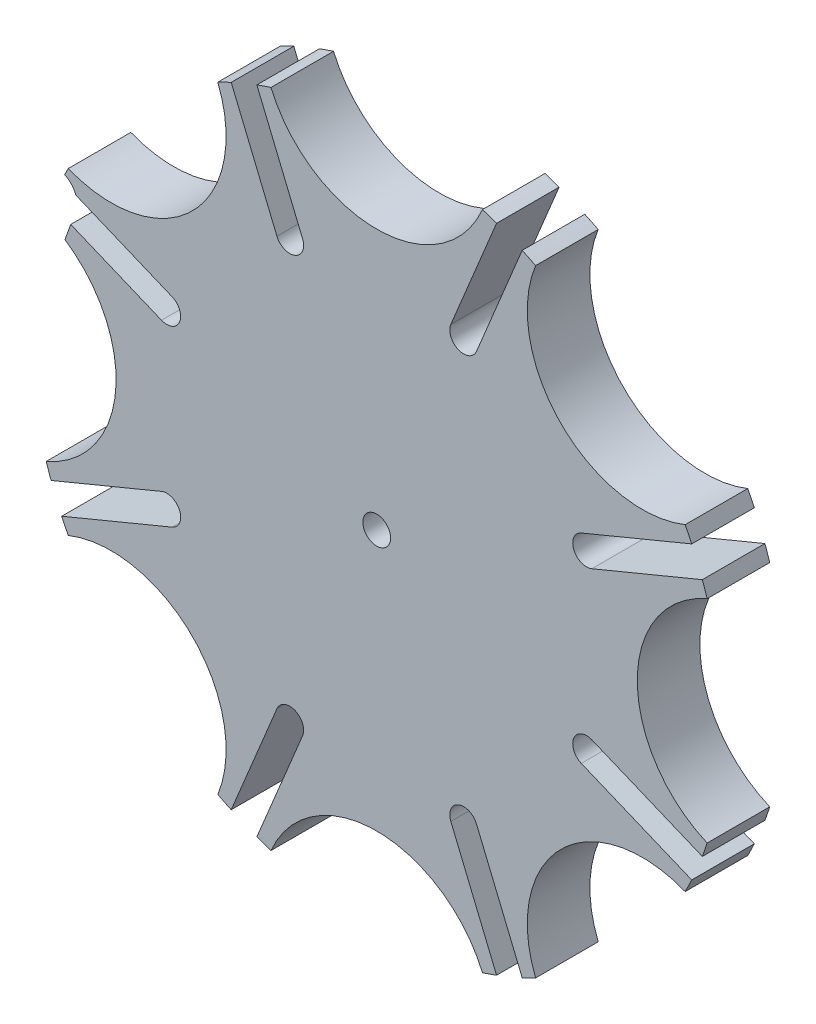
SolidWorks part; units mm, degrees
ref_plane "Front Plane" through (0, 0, 0) normal (0, 0, 1) x (1, 0, 0)
ref_plane "Top Plane" through (0, 0, 0) normal (0, 1, 0) x (1, 0, 0)
ref_plane "Right Plane" through (0, 0, 0) normal (1, 0, 0) x (0, 0, -1)
sketch "Croquis1" plane through (0, 0, 0) normal (0, 0, 1) x (1, 0, 0)
  line L0 (0, 0) -> (-15.1187, 6.2624) construction
  line L1 (0, 0) -> (-18, 0) construction
  line L2 (0, 0) -> (33.8007, 14.0007) construction
  line L3 (0, 0) -> (-10.0606, 4.1672)
  line L4 (-10.0606, 4.1672) -> (-15.364, 6.364) construction
  line L5 (-10.3151, 3.5527) -> (-15.6185, 5.7494)
  line L6 (-9.806, 4.7818) -> (-15.1094, 6.9785)
  line L7 (-18, 0) -> (-15.364, 6.364) construction
  line L8 (-4.1672, 10.0606) -> (-6.364, 15.364) construction
  line L9 (-4.7818, 9.806) -> (-6.9785, 15.1094)
  line L10 (-3.5527, 10.3151) -> (-5.7494, 15.6185)
  line L11 (4.1672, 10.0606) -> (6.364, 15.364) construction
  line L12 (3.5527, 10.3151) -> (5.7494, 15.6185)
  line L13 (4.7818, 9.806) -> (6.9785, 15.1094)
  line L14 (10.0606, 4.1672) -> (15.364, 6.364) construction
  line L45 (-16.2663, 6.7899) -> (-19.2031, 0.5679)
  line L46 (-16.7477, -0.4492) -> (-14.4248, 6.0271)
  line L60 (9.806, 4.7818) -> (15.1094, 6.9785)
  line L75 (10.3151, 3.5527) -> (15.6185, 5.7494)
  line L82 (10.0606, -4.1672) -> (15.364, -6.364) construction
  line L85 (10.3151, -3.5527) -> (15.6185, -5.7494)
  line L88 (9.806, -4.7818) -> (15.1094, -6.9785)
  line L91 (4.1672, -10.0606) -> (6.364, -15.364) construction
  line L92 (4.7818, -9.806) -> (6.9785, -15.1094)
  line L93 (3.5527, -10.3151) -> (5.7494, -15.6185)
  line L94 (-4.1672, -10.0606) -> (-6.364, -15.364) construction
  line L95 (-3.5527, -10.3151) -> (-5.7494, -15.6185)
  line L96 (-4.7818, -9.806) -> (-6.9785, -15.1094)
  line L97 (-10.0606, -4.1672) -> (-15.364, -6.364) construction
  line L98 (-9.806, -4.7818) -> (-15.1094, -6.9785)
  line L99 (-10.3151, -3.5527) -> (-15.6185, -5.7494)
  circle A0 centre (0, 0) radius 16.6298
  circle A7 centre (-18, 0) radius 5.5106
  arc A8 (-10.3151, 3.5527) -> (-9.806, 4.7818) centre (-10.0606, 4.1672) ccw
  arc A9 (-15.1094, 6.9785) -> (-15.6185, 5.7494) centre (-15.364, 6.364) ccw
  circle A10 centre (-12.7279, 12.7279) radius 5.5106
  arc A11 (-4.7818, 9.806) -> (-3.5527, 10.3151) centre (-4.1672, 10.0606) ccw
  arc A12 (-5.7494, 15.6185) -> (-6.9785, 15.1094) centre (-6.364, 15.364) ccw
  circle A13 centre (0, 18) radius 5.5106
  arc A14 (3.5527, 10.3151) -> (4.7818, 9.806) centre (4.1672, 10.0606) ccw
  arc A15 (6.9785, 15.1094) -> (5.7494, 15.6185) centre (6.364, 15.364) ccw
  circle A52 centre (-18, 0) radius 1.3304
  circle A53 centre (-15.364, 6.364) radius 0.9978
  circle A54 centre (0, 0) radius 0.6652
  arc A55 (-12.4894, 0) -> (-22.5301, 3.1377) centre (-12.4894, 17.6341) cw
  circle A56 centre (-18, 0) radius 0.6652
  circle A57 centre (-15.364, 6.364) radius 0.6652
  circle A115 centre (12.7279, 12.7279) radius 5.5106
  arc A116 (9.806, 4.7818) -> (10.3151, 3.5527) centre (10.0606, 4.1672) ccw
  arc A117 (15.6185, 5.7494) -> (15.1094, 6.9785) centre (15.364, 6.364) ccw
  circle A118 centre (18, 0) radius 5.5106
  arc A119 (10.3151, -3.5527) -> (9.806, -4.7818) centre (10.0606, -4.1672) ccw
  arc A120 (15.1094, -6.9785) -> (15.6185, -5.7494) centre (15.364, -6.364) ccw
  circle A121 centre (12.7279, -12.7279) radius 5.5106
  arc A122 (4.7818, -9.806) -> (3.5527, -10.3151) centre (4.1672, -10.0606) ccw
  arc A123 (5.7494, -15.6185) -> (6.9785, -15.1094) centre (6.364, -15.364) ccw
  circle A124 centre (0, -18) radius 5.5106
  arc A125 (-3.5527, -10.3151) -> (-4.7818, -9.806) centre (-4.1672, -10.0606) ccw
  arc A126 (-6.9785, -15.1094) -> (-5.7494, -15.6185) centre (-6.364, -15.364) ccw
  circle A127 centre (-12.7279, -12.7279) radius 5.5106
  arc A128 (-9.806, -4.7818) -> (-10.3151, -3.5527) centre (-10.0606, -4.1672) ccw
  arc A129 (-15.6185, -5.7494) -> (-15.1094, -6.9785) centre (-15.364, -6.364) ccw
  point P4 (-12.7123, 5.2656)
  point P14 (12.7123, 5.2656)
  point P15 (0, 0)
  point P18 (-15.364, 6.364)
  point P20 (-5.2656, 12.7123)
  point P29 (5.2656, 12.7123)
  point P44 (12.7123, -5.2656)
  point P47 (0, 0)
  point P55 (5.2656, -12.7123)
  point P64 (-5.2656, -12.7123)
  point P73 (-12.7123, -5.2656)
  dimension "D4" = 11.0213
  dimension "D8" = 0.6652
  dimension "D3" = 2.6608
  dimension "D9" = 1.3304
  dimension "D11" = 1.9956
  dimension "D12" = 17.6341
  dimension "D13" = 1.3304
  dimension "D1" = 18
  dimension "D2" = 22.5
  dimension "D5" = 45
  dimension "D6" = 36.5856
  dimension "D7" = 10.8895
  dimension "D10" = 8
extrude "Saliente-Extruir1" add sketch "Croquis1" against normal blind 3 contours A0 L13 A14 L12 A13 L10 A11 L9 A10 L6 A8 L5 A7 region at (-9.0321, 4.5932, 0)
sketch "Croquis4" [suppressed] plane through (0, 0, 0) normal (0, 0, 1) x (1, 0, 0)
  circle A0 centre (-18, 0) radius 4.9251 construction
  arc A1 (-22.0487, 2.8043) -> (-13.0749, 0) centre (-13.0749, 15.7603) ccw construction
  arc A2 (-22.0487, 2.8043) -> (-13.0749, 0) centre (-18, 0) ccw
  arc A3 (-22.0487, 2.8043) -> (-13.0749, 0) centre (-13.0749, 15.7603) ccw
  circle A4 centre (-18, 0) radius 0.6766 construction
  circle A5 centre (-18, 0) radius 0.6766
  circle A7 centre (-15.8944, 5.7851) radius 0.6766 construction
  circle A9 centre (-15.8944, 5.7851) radius 0.6766
extrude "Saliente-Extruir4" [suppressed] add sketch "Croquis4" against normal blind 3
sketch "Croquis6" [suppressed] plane through (0, 0, 0) normal (0, 0, 1) x (1, 0, 0)
  line L0 (-16.7049, -0.3922) -> (-14.9231, 5.4909) construction
  line L1 (-16.8275, 6.1841) -> (-19.2442, 0.532) construction
  line L2 (-16.7049, -0.3922) -> (-14.9231, 5.4909)
  line L3 (-16.8275, 6.1841) -> (-19.2442, 0.532)
  circle A0 centre (-15.8944, 5.7851) radius 1.0149 construction
  circle A1 centre (-18, 0) radius 1.3532 construction
  arc A2 (-14.9231, 5.4909) -> (-16.8275, 6.1841) centre (-15.8944, 5.7851) ccw
  arc A3 (-19.2442, 0.532) -> (-16.7049, -0.3922) centre (-18, 0) ccw
  circle A6 centre (-18, 0) radius 0.6766 construction
  circle A7 centre (-18, 0) radius 0.6766
extrude "Saliente-Extruir5" [suppressed] add sketch "Croquis6" along normal blind 3
sketch "Croquis7" [suppressed] plane through (0, 0, 0) normal (0, 0, 1) x (1, 0, 0)
  circle A0 centre (0, 0) radius 0.6766 construction
  circle A1 centre (-18, 0) radius 0.6766 construction
  circle A2 centre (0, 0) radius 0.6766
  circle A3 centre (-18, 0) radius 0.6766
extrude "Saliente-Extruir6" [suppressed] add sketch "Croquis7" against normal blind 18 and the other way blind 3
sketch "Croquis8" [suppressed] plane through (0, 0, -18) normal (0, 0, -1) x (-1, 0, 0)
  line L0 (0, -4.9251) -> (18, -4.9251)
  line L1 (0, 4.9251) -> (18, 4.9251)
  circle A0 centre (18, 0) radius 4.9251 construction
  arc A1 (18, -4.9251) -> (18, 4.9251) centre (18, 0) ccw
  arc A2 (0, 4.9251) -> (0, -4.9251) centre (0, 0) ccw
extrude "Saliente-Extruir7" [suppressed] add sketch "Croquis8" along normal blind 6
equation "\"S\"= ( \"d\" - \"a\" ) * 0.98"
equation "\"R\"= \"d\" * cos ( \"Bo\" / 2 ) * 2"
equation "\"n\"= 8"
equation "\"Bo\"= 360 / \"n\""
equation "\"din\"= \"d\" / 10"
equation "\"d\"=18"
equation "\"D4@Croquis1\"= \"D2\""
equation "\"D1@Croquis1\"=\"d\""
equation "\"D2@Croquis1\"=\"Bo\"/2"
equation "\"D5@Croquis1\"=\"Bo\""
equation "\"D6@Croquis1\"=\"R\"*1.1"
equation "\"D7@Croquis1\"=\"S\""
equation "\"R1\"= \"R\" / 50"
equation "\"D8@Croquis1\"=\"R1\""
equation "\"a\"= \"d\" * sin ( \"Bo\" / 2 )"
equation "\"ancho\"= 3"
equation "\"D1@Saliente-Extruir1\"=\"ancho\""
equation "\"D10@Croquis1\"=\"n\""
equation "\"D2\"= 1.6 * \"a\""
equation "\"D3@Croquis1\"=4*\"R1\""
equation "\"D9@Croquis1\"=2*\"R1\""
equation "\"D11@Croquis1\"=3*\"R1\""
equation "\"D12@Croquis1\"=\"D2\"/2*3.2"
equation "\"D13@Croquis1\"=2*\"R1\""
equation "\"D1@Saliente-Extruir7\"=\"ancho\"*2"
equation "\"D1@Saliente-Extruir6\"=\"ancho\"*6"
equation "\"D2@Saliente-Extruir6\"=\"ancho\""
equation "\"D1@Saliente-Extruir5\"=\"ancho\""
equation "\"D1@Saliente-Extruir4\"=\"ancho\""
